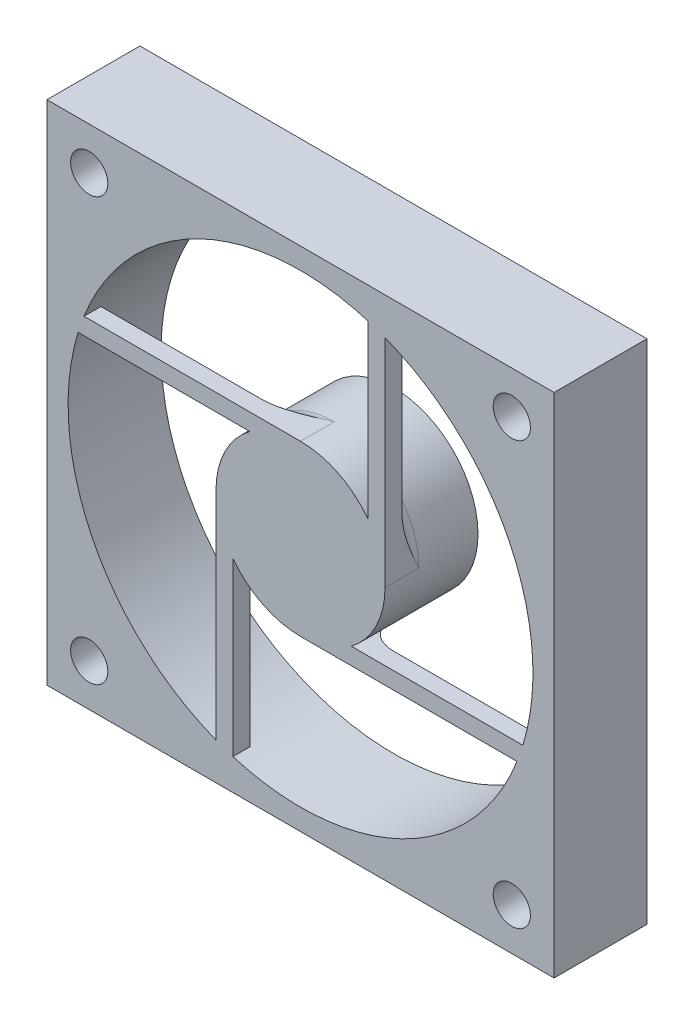
SolidWorks part; units mm, degrees
material "PBT Общее назначение"
ref_plane "Спереди" through (0, 0, 0) normal (0, 0, 1) x (1, 0, 0)
ref_plane "Сверху" through (0, 0, 0) normal (0, 1, 0) x (1, 0, 0)
ref_plane "Справа" through (0, 0, 0) normal (1, 0, 0) x (0, 0, -1)
sketch "Эскиз1" plane through (0, 0, 0) normal (0, 0, 1) x (1, 0, 0)
  line L0 (0, 0) -> (60, 0)
  line L1 (0, 0) -> (0, 60)
  line L2 (60, 0) -> (60, 60)
  line L3 (0, 60) -> (60, 60)
  line L4 (5, 55) -> (55, 55) construction
  line L5 (5, 55) -> (5, 5) construction
  line L6 (55, 55) -> (55, 5) construction
  line L7 (5, 5) -> (55, 5) construction
  line L8 (30, 60) -> (30, 0) construction
  line L9 (60, 30) -> (0, 30) construction
  circle A0 centre (5, 55) radius 2.2
  circle A1 centre (55, 55) radius 2.2
  circle A2 centre (5, 5) radius 2.2
  circle A3 centre (55, 5) radius 2.2
  circle A4 centre (30, 30) radius 27.5
  point P13 (5, 30)
  point P14 (30, 55)
  dimension "D5" = 4.4
  dimension "D6" = 55
  dimension "D1" = 60
  dimension "D2" = 60
  dimension "D3" = 50
  dimension "D4" = 50
extrude "Бобышка-Вытянуть1" add sketch "Эскиз1" along normal blind 11
sketch "Эскиз2" plane through (0, 0, 11) normal (0, 0, 1) x (1, 0, 0)
  circle A0 centre (30, 30) radius 10
  dimension "D1" = 20
extrude "Бобышка-Вытянуть2" add sketch "Эскиз2" against normal up to surface (11 mm away) separate body up to face at (57.2, 5, 0)
sketch "Эскиз3" plane through (0, 0, 11) normal (0, 0, 1) x (1, 0, 0)
  line L0 (40, 30) -> (38, 30)
  line L1 (40, 30) -> (40, 60)
  line L2 (38, 30) -> (38, 60)
  line L3 (40, 60) -> (38, 60)
  line L5 (30, 40) -> (30, 38)
  line L6 (30, 40) -> (0, 40)
  line L7 (30, 38) -> (0, 38)
  line L8 (0, 40) -> (0, 38)
  line L9 (20, 30) -> (22, 30)
  line L10 (20, 30) -> (20, 0)
  line L11 (22, 30) -> (22, 0)
  line L12 (20, 0) -> (22, 0)
  line L13 (30, 20) -> (30, 22)
  line L14 (30, 20) -> (60, 20)
  line L15 (30, 22) -> (60, 22)
  line L16 (60, 20) -> (60, 22)
  line L20 (60, 0) -> (60, 60) construction
  line L21 (0, 0) -> (60, 0) construction
  line L22 (0, 60) -> (0, 0) construction
  line L23 (60, 60) -> (0, 60) construction
  circle A1 centre (30, 30) radius 10 construction
  dimension "D1" = 2
extrude "Бобышка-Вытянуть3" add sketch "Эскиз3" against normal blind 2
combine bodies "Соединить1" operation type add bodies to combine 104 105
fillet "Скругление1" radius 2 4 edges at (33.1623, 20.5132, 9) (20.5132, 26.8377, 9) (39.4868, 33.1623, 9) (26.8377, 39.4868, 9)
sketch "Эскиз4" plane through (0, 0, 11) normal (0, 0, 1) x (1, 0, 0)
  line L0 (30, 60) -> (30, 0) construction
  line L1 (60, 60) -> (0, 60) construction
  line L2 (0, 0) -> (60, 0) construction
  line L3 (0, 30) -> (60, 30) construction
  line L4 (0, 60) -> (0, 0) construction
  line L5 (60, 0) -> (60, 60) construction
